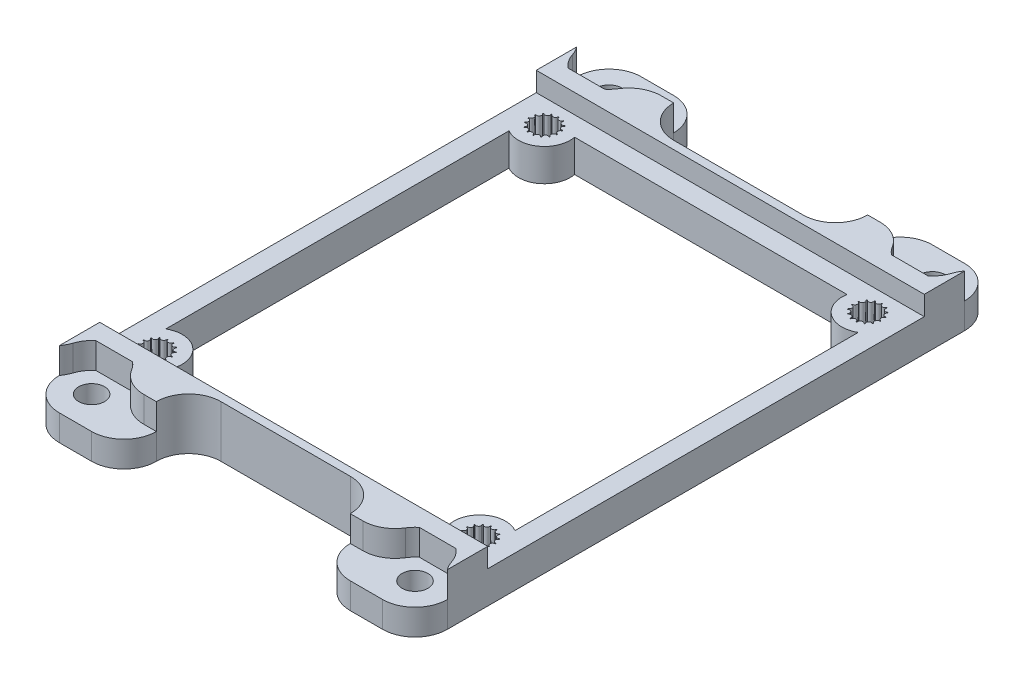
SolidWorks part; units mm, degrees
ref_plane "Front Plane" through (0, 0, 0) normal (0, 0, 1) x (1, 0, 0)
ref_plane "Top Plane" through (0, 0, 0) normal (0, 1, 0) x (1, 0, 0)
ref_plane "Right Plane" through (0, 0, 0) normal (1, 0, 0) x (0, 0, -1)
sketch "Sketch1" plane through (0, 0, 0) normal (0, 1, 0) x (1, 0, 0)
  line L1 (0, 0) -> (60, 0)
  line L2 (0, 0) -> (0, 70)
  line L3 (0, 70) -> (60, 70)
  line L4 (60, 0) -> (60, 70)
  dimension "D1" = 60
  dimension "D2" = 70
extrude "Boss-Extrude1" add sketch "Sketch1" along normal blind 8
sketch "Sketch2" plane through (0, 8, 0) normal (0, 1, 0) x (1, 0, 0)
  line L4 (0, 70) -> (0, 0)
  line L5 (0, 0) -> (60, 0)
  line L6 (60, 0) -> (60, 70)
  line L7 (60, 70) -> (0, 70)
  line L8 (0, 70) -> (0, 0)
  line L9 (0, 0) -> (60, 0)
  line L10 (60, 0) -> (60, 70)
  line L11 (60, 70) -> (0, 70)
  circle A0 centre (5, 5) radius 2.25
  circle A1 centre (5, 7.25) radius 0.4
  circle A2 centre (5.9152, 7.0555) radius 0.4
  circle A3 centre (6.6721, 6.5055) radius 0.4
  circle A4 centre (7.1399, 5.6953) radius 0.4
  circle A5 centre (7.2377, 4.7648) radius 0.4
  circle A6 centre (6.9486, 3.875) radius 0.4
  circle A7 centre (6.3225, 3.1797) radius 0.4
  circle A8 centre (5.4678, 2.7992) radius 0.4
  circle A9 centre (4.5322, 2.7992) radius 0.4
  circle A10 centre (3.6775, 3.1797) radius 0.4
  circle A11 centre (3.0514, 3.875) radius 0.4
  circle A12 centre (2.7623, 4.7648) radius 0.4
  circle A13 centre (2.8601, 5.6953) radius 0.4
  circle A14 centre (3.3279, 6.5055) radius 0.4
  circle A15 centre (4.0848, 7.0555) radius 0.4
  point P38 (5, 5)
  dimension "D4" = 4.5
  dimension "D5" = 0.8
  dimension "D2" = 5
  dimension "D3" = 5
  dimension "D1" = 0
  dimension "D6" = 15
extrude "Cut-Extrude1" cut sketch "Sketch2" against normal blind 8 contours A15 A0 A14 A13 A12 A11 A10 A9 A8 A7 A6 A5 A4 A3 A2 A1
ref_plane "Plane1" through (30, 0, 0) normal (-1, 0, 0) x (0, 0, 1)
ref_plane "Plane2" through (0, 0, -35) normal (0, 0, -1) x (-1, 0, 0)
mirror "Mirror1" about plane through (0, 0, -35) normal (0, 0, -1) of "Cut-Extrude1" second plane through (30, 0, 0) second plane normal (-1, 0, 0)
sketch "Sketch3" plane through (0, 8, 0) normal (0, 1, 0) x (1, 0, 0)
  line L1 (0, 0) -> (15, 0)
  line L2 (0, 0) -> (0, -10)
  line L3 (0, -10) -> (15, -10)
  line L4 (15, 0) -> (15, -10)
  circle A0 centre (5, -5) radius 2
  dimension "D3" = 4
  dimension "D1" = 10
  dimension "D2" = 15
  dimension "D4" = 5
extrude "Boss-Extrude2" add sketch "Sketch3" against normal blind 8
mirror "Mirror2" about plane through (0, 0, -35) normal (0, 0, -1) of "Boss-Extrude2" second plane through (30, 0, 0) second plane normal (-1, 0, 0)
fillet "Fillet1" radius 5 20 edges at (0, 4, 10) (15, 0, 5) (15, 4, 0) (15, 4, 10) (15, 8, 5) (45, 0, 5) (60, 4, 10) (45, 8, 5) (45, 4, 10) (45, 4, 0) (15, 0, -75) (0, 4, -80) (15, 8, -75) (15, 4, -80) (15, 4, -70) (60, 4, -80) (45, 0, -75) (45, 4, -70) (45, 4, -80) (45, 8, -75)
sketch "Sketch4" plane through (0, 8, 0) normal (0, 1, 0) x (1, 0, 0)
  line L0 (0.5, -5) -> (0, -5)
  line L1 (0, -5) -> (0.5, -5)
  line L2 (9.5, -5) -> (15, -5)
  line L3 (15, -5) -> (15, -11.0585)
  line L4 (15, -11.0585) -> (0, -11.0585)
  line L5 (0, -11.0585) -> (0, -5)
  line L6 (2.1716, -1.5) -> (7.8284, -1.5)
  arc A0 (9.5, -5) -> (0.5, -5) centre (5, -5) ccw
  dimension "D1" = 9
  dimension "D2" = 3.5
extrude "Cut-Extrude2" cut sketch "Sketch4" against normal blind 4 contours L2 A0 L0 L5 L4 L3
mirror "Mirror4" about plane through (0, 0, -35) normal (0, 0, -1) of "Cut-Extrude2" second plane through (30, 0, 0) second plane normal (-1, 0, 0)
fillet "Fillet2" radius 5 8 edges at (9.5, 6, 5) (0.5, 6, 5) (50.5, 6, 5) (59.5, 6, 5) (9.5, 6, -75) (0.5, 6, -75) (50.5, 6, -75) (59.5, 6, -75)
sketch "Sketch5" plane through (0, 8, 0) normal (0, 1, 0) x (1, 0, 0)
  line L0 (4.4, 35) -> (-4.4, 35) construction
  line L1 (10, 60) -> (50, 60)
  line L2 (10, 60) -> (10, 10)
  line L3 (10, 10) -> (50, 10)
  line L4 (50, 60) -> (50, 10)
  line L5 (10, 60) -> (50, 10) construction
  line L6 (10, 10) -> (50, 60) construction
  line L7 (30, 4.4) -> (30, -4.4) construction
  line L8 (60, -5) -> (60, 75) construction
  line L9 (40, 70) -> (20, 70) construction
  point P0 (30, 35)
  dimension "D1" = 10
  dimension "D2" = 10
extrude "Cut-Extrude3" cut sketch "Sketch5" against normal blind 13
sketch "Sketch6" plane through (0, 8, 0) normal (0, 1, 0) x (1, 0, 0)
  line L0 (30, 35) -> (30, 39.1049) construction
  line L1 (4.4, 35) -> (-4.4, 35) construction
  line L2 (30, 4.4) -> (30, -4.4) construction
  line L3 (30, 39.1049) -> (30, 32.7104) construction
  line L4 (30, 32.7104) -> (30, 35) construction
  line L5 (30, 35) -> (28.2898, 35) construction
  line L6 (28.2898, 35) -> (34.1342, 35) construction
  line L8 (-1, 1.25) -> (61, 1.25)
  line L9 (-1, 1.25) -> (-1, 68.75)
  line L10 (-1, 68.75) -> (61, 68.75)
  line L11 (61, 1.25) -> (61, 68.75)
  line L12 (-1, 1.25) -> (61, 68.75) construction
  line L13 (-1, 68.75) -> (61, 1.25) construction
  dimension "D1" = 67.5
  dimension "D2" = 62
extrude "Cut-Extrude4" cut sketch "Sketch6" against normal blind 3
sketch "Sketch7" plane through (0, 5, 0) normal (0, 1, 0) x (1, 0, 0)
  line L0 (4.4, 35) -> (-4.4, 35) construction
  line L1 (60, 1.25) -> (0, 1.25)
  line L2 (60, 1.25) -> (60, 68.75)
  line L3 (60, 68.75) -> (0, 68.75)
  line L4 (0, 1.25) -> (0, 68.75)
  line L5 (60, 1.25) -> (0, 68.75) construction
  line L6 (60, 68.75) -> (0, 1.25) construction
  line L7 (60, 68.75) -> (60, 1.25) construction
  line L8 (57, 65.75) -> (3, 65.75)
  line L9 (3, 4.25) -> (3, 65.75)
  line L10 (57, 4.25) -> (3, 4.25)
  line L11 (57, 4.25) -> (57, 65.75)
  line L12 (30, 4.4) -> (30, -4.4) construction
  arc A1 (3, 61.5359) -> (8.9291, 65.75) centre (5, 65) ccw
  arc A2 (57, 61.5359) -> (51.0709, 65.75) centre (55, 65) cw
  arc A3 (57, 8.4641) -> (51.0709, 4.25) centre (55, 5) ccw
  arc A4 (3, 8.4641) -> (8.9291, 4.25) centre (5, 5) cw
  point P0 (30, 35)
  dimension "D4" = 8
  dimension "D1" = 3
extrude "Cut-Extrude5" cut sketch "Sketch7" against normal blind 14
